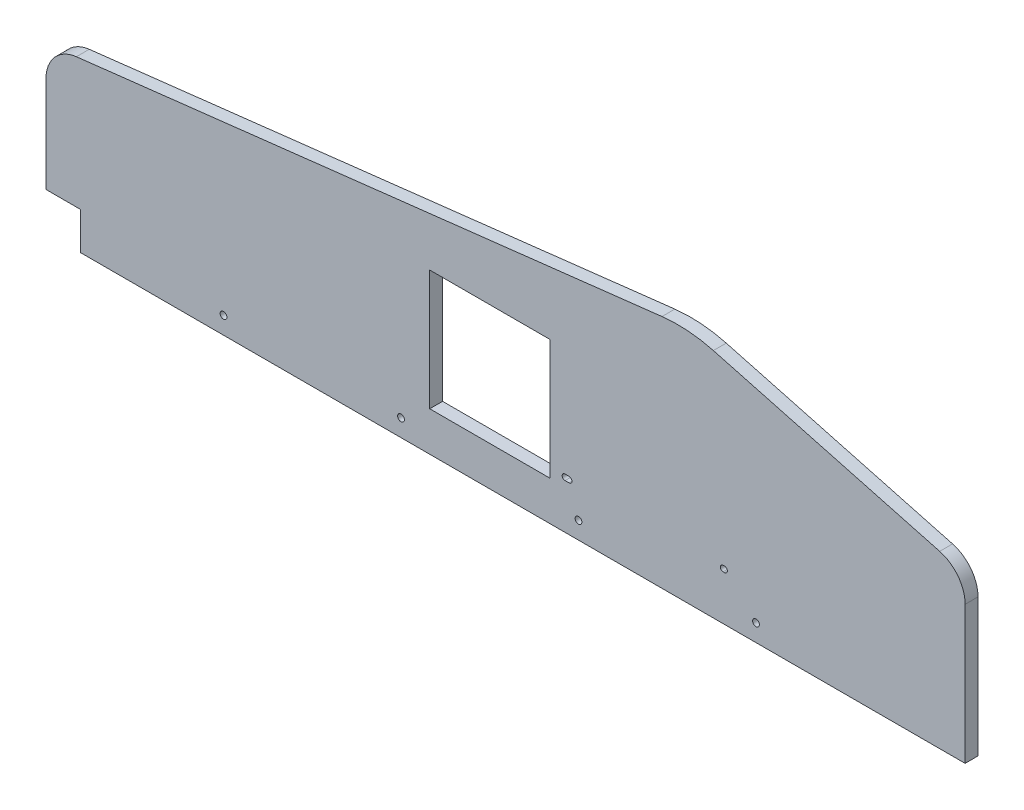
SolidWorks part; units mm, degrees
material "PC High Viscosity"
ref_plane "Front Plane" through (0, 0, 0) normal (0, 0, 1) x (1, 0, 0)
ref_plane "Top Plane" through (0, 0, 0) normal (0, 1, 0) x (1, 0, 0)
ref_plane "Right Plane" through (0, 0, 0) normal (1, 0, 0) x (0, 0, -1)
sketch "Sketch2" plane through (0, 0, 0) normal (0, 0, 1) x (1, 0, 0)
  line L0 (-340, 26.4) -> (-340, 121.4)
  line L1 (-340, 121.4) -> (135, 176.4)
  line L2 (135, 176.4) -> (340, 121.4)
  line L3 (340, 121.4) -> (340, 26.4)
  line L4 (340, 26.4) -> (340, 0)
  line L6 (340, 0) -> (-340, 0)
  line L7 (-340, 0) -> (-340, 26.4)
  dimension "D1" = 150
  dimension "D2" = 680
  dimension "D3" = 95
  dimension "D4" = 475
  dimension "D8" = 95
  dimension "D9" = 26.4
extrude "Boss-Extrude1" add sketch "Sketch2" along normal mid plane 9.525
fillet "Fillet1" radius 25.4 2 edges at (340, 121.4, 0) (-340, 121.4, 0)
fillet "Fillet2" radius 101.6 1 edges at (135, 176.4, 0)
sketch "Sketch3" plane through (0, 0, 4.7625) normal (0, 0, 1) x (1, 0, 0)
  line L0 (0, 0) -> (0, 192.0016) construction
  line L1 (-340, 0) -> (-314.6, 0)
  line L2 (-340, 0) -> (-340, 27.686)
  line L3 (-340, 27.686) -> (-314.6, 27.686)
  line L4 (-314.6, 0) -> (-314.6, 27.686)
  line L5 (0, 192.0016) -> (0, -60.0751) construction
  dimension "D1" = 25.4
  dimension "D2" = 27.686
extrude "Cut-Extrude1" cut sketch "Sketch3" against normal through all
sketch "Sketch5" plane through (0, 0, 4.7625) normal (0, 0, 1) x (1, 0, 0)
  line L1 (-56.1185, 118.0465) -> (32.7815, 118.0465)
  line L2 (-56.1185, 118.0465) -> (-56.1185, 29.1465)
  line L3 (-56.1185, 29.1465) -> (32.7815, 29.1465)
  line L4 (32.7815, 118.0465) -> (32.7815, 29.1465)
  line L5 (-56.1185, 118.0465) -> (32.7815, 29.1465) construction
  line L6 (-56.1185, 29.1465) -> (32.7815, 118.0465) construction
  point P0 (-11.6685, 73.5965)
  dimension "D1" = 88.9
  dimension "D2" = 88.9
extrude "Cut-Extrude2" cut sketch "Sketch5" against normal through all
hole_wizard "Tap Drill for M6x1.0 Tap1" positions "Sketch7" profile "Sketch6" hole size "M6x1.0" standard "ANSI Metric" end condition through all
sketch "Sketch7" plane through (0, 0, 4.7625) normal (0, 0, 1) x (1, 0, 0)
  line L0 (-314.6, 0) -> (340, 0) construction
  line L1 (-340, 98.7713) -> (-340, 27.686) construction
  point P0 (-208.682, 12.7)
  point P2 (-77.364, 12.7)
  point P4 (53.954, 12.7)
  point P6 (185.272, 12.7)
  dimension "D1" = 12.7
  dimension "D2" = 131.318
  dimension "D3" = 131.318
  dimension "D4" = 131.318
  dimension "D5" = 131.318
sketch "Sketch6" plane through (-208.682, 12.7, 4.7625) normal (1, 0, 0) x (0, -1, 0)
  line L0 (0, 0) -> (0, 9.525)
  line L1 (0, 9.525) -> (2.5, 9.525)
  line L2 (2.5, 9.525) -> (2.5, 0)
  line L5 (2.5, 0) -> (0, 0)
  line L11 (0, -6.35) -> (0, 107.95) construction
  dimension "Thru Hole Dia." = 5
  dimension "Thru Hole Depth" = 9.525
sketch "Sketch8" plane through (0, 0, 4.7625) normal (0, 0, 1) x (1, 0, 0)
  line L0 (161, 35.3) -> (162, 35.3) construction
  line L1 (161, 37.4) -> (162, 37.4)
  line L2 (161, 33.2) -> (162, 33.2)
  line L3 (47, 35.3) -> (44, 35.3) construction
  line L4 (47, 33.2) -> (44, 33.2)
  line L5 (47, 37.4) -> (44, 37.4)
  line L6 (-314.6, 0) -> (340, 0) construction
  line L10 (-340, 98.7713) -> (-340, 27.686) construction
  arc A0 (161, 37.4) -> (161, 33.2) centre (161, 35.3) ccw
  arc A1 (162, 33.2) -> (162, 37.4) centre (162, 35.3) ccw
  arc A2 (47, 33.2) -> (47, 37.4) centre (47, 35.3) ccw
  arc A3 (44, 37.4) -> (44, 33.2) centre (44, 35.3) ccw
  point P2 (161.5, 35.3)
  point P9 (45.5, 35.3)
  dimension "D2" = 1
  dimension "D1" = 2.1
  dimension "D3" = 35.3
  dimension "D4" = 384
  dimension "D5" = 115.5
  dimension "D6" = 3
extrude "Cut-Extrude3" cut sketch "Sketch8" against normal through all
